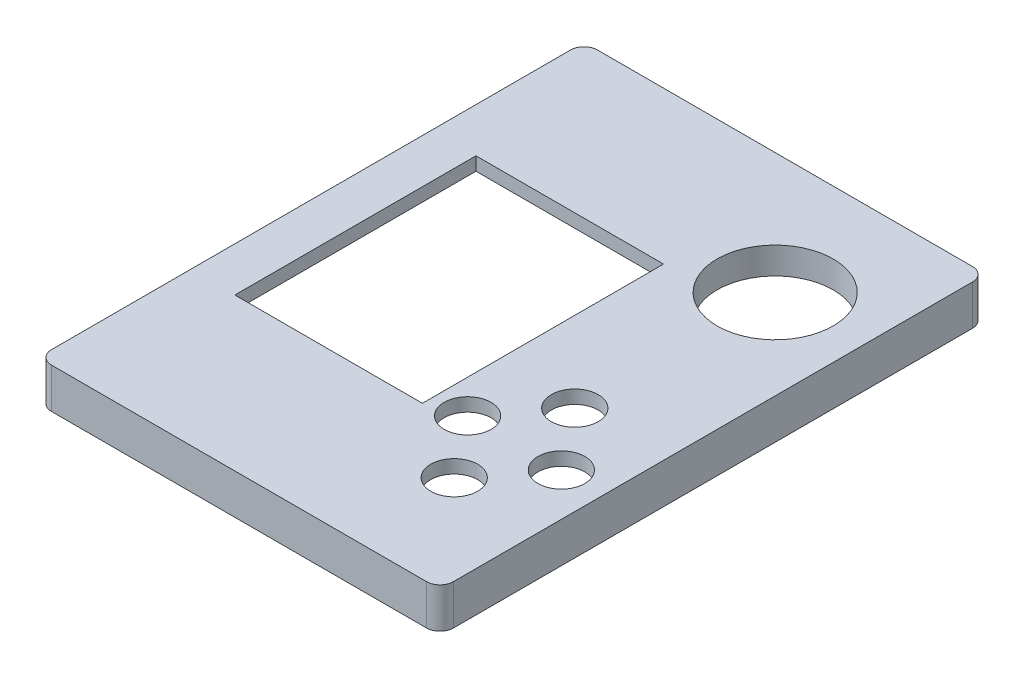
SolidWorks part; units mm, degrees
ref_plane "Front Plane" through (0, 0, 0) normal (0, 0, 1) x (1, 0, 0)
ref_plane "Top Plane" through (0, 0, 0) normal (0, 1, 0) x (1, 0, 0)
ref_plane "Right Plane" through (0, 0, 0) normal (1, 0, 0) x (0, 0, -1)
sketch "Sketch1" plane through (0, 0, 0) normal (0, 1, 0) x (1, 0, 0)
  line L1 (-42, -61.125) -> (42, -61.125)
  line L2 (-45, -58.125) -> (-45, 58.125)
  line L3 (-42, 61.125) -> (42, 61.125)
  line L4 (45, -58.125) -> (45, 58.125)
  line L5 (-45, -61.125) -> (45, 61.125) construction
  line L6 (-45, 61.125) -> (45, -61.125) construction
  arc A0 (42, -61.125) -> (45, -58.125) centre (42, -58.125) ccw
  arc A1 (-42, -61.125) -> (-45, -58.125) centre (-42, -58.125) cw
  arc A2 (42, 61.125) -> (45, 58.125) centre (42, 58.125) cw
  arc A3 (-45, 58.125) -> (-42, 61.125) centre (-42, 58.125) cw
  point P0 (0, 0)
  dimension "D3" = 3
  dimension "D1" = 122.25
  dimension "D2" = 90
extrude "Boss-Extrude1" add sketch "Sketch1" along normal blind 9
sketch "Sketch2" plane through (0, 0, 0) normal (0, -1, 0) x (1, 0, 0)
  line L0 (-45, -58.125) -> (-45, 58.125) construction
  line L2 (42, -61.125) -> (-42, -61.125) construction
  circle A0 centre (-35.959, -52.125) radius 1.45
  circle A1 centre (-35.959, 37.875) radius 1.45
  dimension "D1" = 2.9
  dimension "D4" = 2.9
  dimension "D2" = 9.041
  dimension "D3" = 9
  dimension "D5" = 9.041
  dimension "D6" = 90
extrude "Cut-Extrude1" cut sketch "Sketch2" against normal through all
sketch "Sketch4" plane through (0, 9, 0) normal (0, 1, 0) x (1, 0, 0)
  line L0 (40.9344, -39.875) -> (40.9344, 54.125) construction
  line L1 (37.9344, 57.125) -> (-28.0656, 57.125) construction
  circle A0 centre (24.9344, 34) radius 13
  dimension "D1" = 16
  dimension "D3" = 26
  dimension "D2" = 23.125
extrude "Cut-Extrude2" cut sketch "Sketch4" against normal up to next
ref_plane "Plane1" through (-4.96, 0, 0) normal (-1, 0, 0) x (0, 0, 1)
mirror "Mirror3" about plane through (0, 0, 0) normal (1, 0, 0) of "Cut-Extrude1"
shell "Shell10" thickness 3 removed face at (35.959, 0, -53.575)
sketch "Sketch5" plane through (0, 0, 0) normal (0, -1, 0) x (1, 0, 0)
  circle A1 centre (24.9344, -34) radius 16
  circle A2 centre (24.9344, -34) radius 16
  dimension "D1" = 0
extrude "Cut-Extrude3" cut sketch "Sketch5" against normal blind 3
sketch "Sketch6" plane through (0, 6, 0) normal (0, -1, 0) x (1, 0, 0)
  line L2 (37.9344, -57.125) -> (-28.0656, -57.125) construction
  line L3 (40.9344, 39.875) -> (40.9344, -54.125) construction
  line L4 (-45, -58.125) -> (-45, 58.125) construction
  line L5 (-35.0656, 27) -> (6.9344, 27)
  line L6 (-35.0656, 27) -> (-35.0656, -27)
  line L7 (-35.0656, -27) -> (6.9344, -27)
  line L8 (6.9344, 27) -> (6.9344, -27)
  line L9 (-35.0656, 27) -> (6.9344, -27) construction
  line L10 (-35.0656, -27) -> (6.9344, 27) construction
  circle A0 centre (35.4344, 24.375) radius 5.25
  circle A1 centre (14.4344, 24.375) radius 5.25
  circle A2 centre (24.9344, 10.875) radius 5.25
  circle A3 centre (24.9344, 37.875) radius 5.25
  point P8 (0, 0)
  point P15 (-45, 0)
  point P16 (-17.6062, 0)
  point P17 (-14.0656, 0)
  dimension "D1" = 10.5
  dimension "D5" = 10.5
  dimension "D9" = 10.5
  dimension "D10" = 10.5
  dimension "D2" = 81.5
  dimension "D3" = 5.5
  dimension "D4" = 21
  dimension "D6" = 68
  dimension "D7" = 16
  dimension "D8" = 27
  dimension "D11" = 54
  dimension "D12" = 42
  dimension "D13" = 55
extrude "Cut-Extrude4" cut sketch "Sketch6" against normal up to next
sketch "Sketch7" plane through (0, 9, 0) normal (0, 1, 0) x (1, 0, 0)
  circle A0 centre (-35.959, -37.875) radius 1.45 construction
  circle A1 centre (-35.959, -37.875) radius 1.45
  circle A2 centre (-35.959, 52.125) radius 1.45 construction
  circle A3 centre (-35.959, 52.125) radius 1.45
  circle A4 centre (35.959, 52.125) radius 1.45 construction
  circle A5 centre (35.959, 52.125) radius 1.45
  circle A6 centre (35.959, -37.875) radius 1.45 construction
  circle A7 centre (35.959, -37.875) radius 1.45
extrude "Boss-Extrude2" add sketch "Sketch7" against normal blind 2
